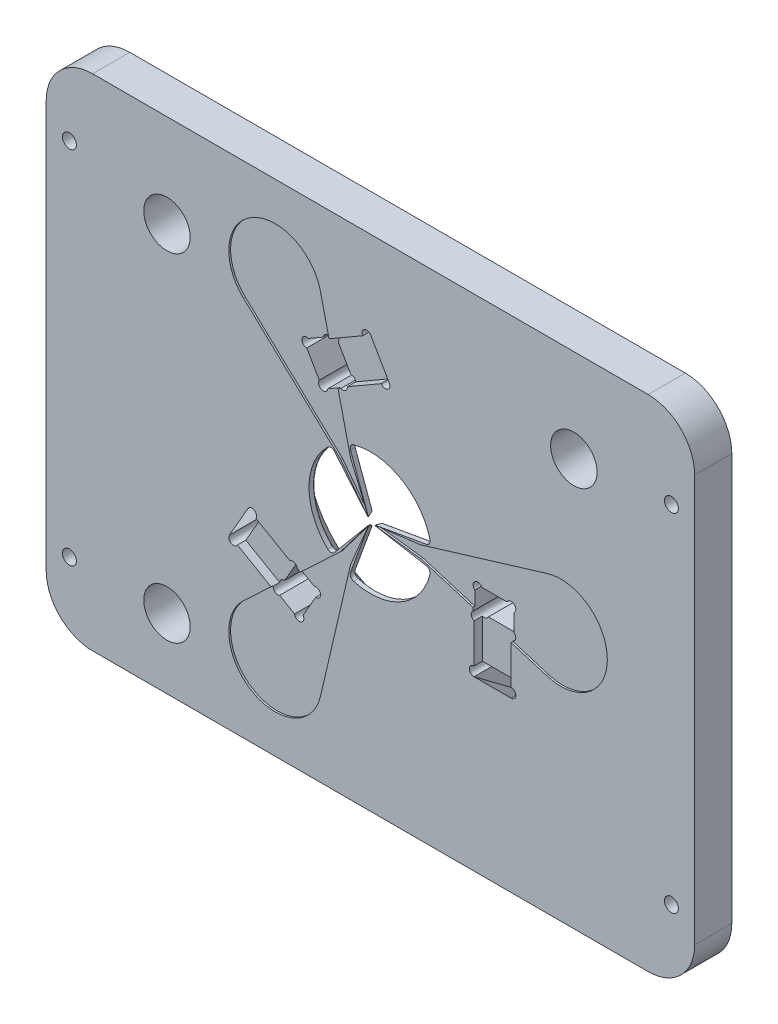
SolidWorks part; units mm, degrees
ref_plane "前基準面" through (0, 0, 0) normal (0, 0, 1) x (1, 0, 0)
ref_plane "上基準面" through (0, 0, 0) normal (0, 1, 0) x (1, 0, 0)
ref_plane "右基準面" through (0, 0, 0) normal (1, 0, 0) x (0, 0, -1)
sketch "草圖1" plane through (0, 0, 0) normal (0, 0, 1) x (1, 0, 0)
  line L1 (-38, 30) -> (38, 30)
  line L2 (-38, 30) -> (-38, -30)
  line L3 (-38, -30) -> (38, -30)
  line L4 (38, 30) -> (38, -30)
  line L5 (-38, 30) -> (38, -30) construction
  line L6 (-38, -30) -> (38, 30) construction
  point P0 (0, 0)
  point P28 (0, 0)
  dimension "D1" = 76
  dimension "D2" = 60
extrude "填料-伸長1" add sketch "草圖1" along normal blind 4
sketch "草圖2" plane through (0, 0, 4) normal (0, 0, 1) x (1, 0, 0)
  line L6 (0.3574, 0.005) -> (20.1903, 2.4807) construction
  line L7 (0.3574, -0.005) -> (20.1903, -2.4807) construction
  line L8 (0.3574, 0.005) -> (4.5094, 0.5233)
  line L9 (0.3574, -0.005) -> (4.5094, -0.5233)
  line L10 (6.1751, 0.8773) -> (19.0478, 4.7845)
  line L11 (6.1751, -0.8773) -> (19.0478, -4.7845)
  line L12 (-2.3278, -5.7864) -> (-5.3804, -18.8881)
  line L13 (-0.1744, -0.312) -> (-1.8015, -4.1669)
  line L14 (-0.183, -0.307) -> (-2.7079, -3.6436)
  line L15 (-3.8473, -4.9091) -> (-13.6674, -14.1037)
  line L16 (-3.8473, 4.9091) -> (-13.6674, 14.1037)
  line L17 (-0.183, 0.307) -> (-2.7079, 3.6436)
  line L18 (-0.1744, 0.312) -> (-1.8015, 4.1669)
  line L19 (-2.3278, 5.7864) -> (-5.3804, 18.8881)
  circle A7 centre (0, 0) radius 0.353 construction
  arc A8 (0.3574, 0.005) -> (0.3574, -0.005) centre (0.358, 0) ccw
  arc A9 (19.0478, -4.7845) -> (19.0478, 4.7845) centre (20.5, 0) ccw
  circle A10 centre (20.5, 0) radius 2.5 construction
  arc A11 (4.5094, -0.5233) -> (6.1751, -0.8773) centre (3.2707, -10.4463) cw
  arc A12 (4.5094, 0.5233) -> (6.1751, 0.8773) centre (3.2707, 10.4463) ccw
  arc A13 (-13.6674, -14.1037) -> (-5.3804, -18.8881) centre (-10.25, -17.7535) ccw
  arc A14 (-1.8015, -4.1669) -> (-2.3278, -5.7864) centre (7.4114, -8.0556) ccw
  arc A15 (-0.1744, -0.312) -> (-0.183, -0.307) centre (-0.179, -0.31) ccw
  arc A16 (-2.7079, -3.6436) -> (-3.8473, -4.9091) centre (-10.6821, 2.3906) cw
  arc A17 (-5.3804, 18.8881) -> (-13.6674, 14.1037) centre (-10.25, 17.7535) ccw
  arc A18 (-2.7079, 3.6436) -> (-3.8473, 4.9091) centre (-10.6821, -2.3906) ccw
  arc A19 (-0.183, 0.307) -> (-0.1744, 0.312) centre (-0.179, 0.31) ccw
  arc A20 (-1.8015, 4.1669) -> (-2.3278, 5.7864) centre (7.4114, 8.0556) cw
  point P17 (5.3574, -0.6291)
  point P20 (5.3574, 0.6291)
  point P46 (0, 0)
  dimension "D1" = 0.706
  dimension "D2" = 0.01
  dimension "D3" = 10
  dimension "D6" = 5
  dimension "D4" = 5
  dimension "D7" = 10
  dimension "D9" = 0.6201
  dimension "D5" = 20.5
  dimension "D8" = 3
extrude "除料-伸長1" cut sketch "草圖2" against normal blind 0.5
sketch "草圖5" plane through (0, 0, 4) normal (0, 0, 1) x (1, 0, 0)
  line L0 (-29.9, 26.9) -> (29.9, 26.9)
  line L1 (-38, 30) -> (-38, -30) construction
  line L2 (38, -30) -> (38, 30) construction
  line L3 (34.9, 21.9) -> (34.9, -21.9)
  line L4 (38, 30) -> (-38, 30) construction
  line L5 (-38, -30) -> (38, -30) construction
  line L6 (-29.9, -26.9) -> (29.9, -26.9)
  line L7 (-34.9, 21.9) -> (-34.9, -21.9)
  arc A0 (-29.9, -26.9) -> (-34.9, -21.9) centre (-29.9, -21.9) cw
  arc A1 (34.9, -21.9) -> (29.9, -26.9) centre (29.9, -21.9) cw
  arc A2 (29.9, 26.9) -> (34.9, 21.9) centre (29.9, 21.9) cw
  arc A3 (-34.9, 21.9) -> (-29.9, 26.9) centre (-29.9, 21.9) cw
  line M29 (38, -30) -> (38, 30)
  line M30 (38, 30) -> (-38, 30)
  line M31 (-38, 30) -> (-38, -30)
  line M32 (-38, -30) -> (38, -30)
  dimension "D5" = 5
  dimension "D1" = 3.1
  dimension "D2" = 3.1
  dimension "D3" = 3.1
  dimension "D4" = 3.1
extrude "除料-伸長4" cut sketch "草圖5" against normal blind 10 contours L7 A3 L0 A2 L3 A1 L6 A0 M32 M29 M30 M31 region at (0, -29.0317, 4)
ref_plane "平面1" through (0, 0, 4) normal (0, 0, 1) x (1, 0, 0)
sketch "草圖7" plane through (0, 0, 4) normal (0, 0, 1) x (1, 0, 0)
  line L0 (0, 0) -> (34.9, 0) construction
  line L1 (34.9, 21.9) -> (34.9, -21.9) construction
  line L2 (11.05, -0.2286) -> (15.25, -0.2286)
  line L3 (15.25, -0.2286) -> (15.25, -3.3286)
  line L4 (15.25, -3.3286) -> (11.05, -3.3286)
  line L5 (11.05, -3.3286) -> (11.05, -0.2286)
  line L6 (11.05, -1.7786) -> (15.25, -1.7786) construction
  line L7 (13.15, -0.2286) -> (13.15, -3.3286) construction
  line L8 (13.15, -1.7786) -> (11.05, -0.2286) construction
  line L9 (0, 0) -> (-12.75, -22.0836) construction
  line L10 (-6.575, -11.3882) -> (-6.9709, -11.1597) construction
  line L11 (-5.7229, -9.4553) -> (-7.8229, -13.0926)
  line L16 (-7.4271, 13.3212) -> (-5.3271, 9.6839)
  line L17 (-7.4271, 13.3212) -> (-4.7424, 14.8712)
  line L18 (-4.7424, 14.8712) -> (-2.6424, 11.2339)
  line L23 (13.15, -1.7786) -> (13.15, -13.7786) construction
  line L24 (11.15, -7.7786) -> (15.15, -7.7786)
  line L25 (11.15, -7.7786) -> (11.15, -8.7786)
  line L26 (11.15, -8.7786) -> (15.15, -8.7786)
  line L27 (15.15, -8.7786) -> (15.15, -7.7786)
  line L28 (-2.6424, 11.2339) -> (-5.3271, 9.6839)
  line L33 (-6.0847, 14.0962) -> (-3.9847, 10.4589) construction
  line L34 (11.15, -8.2786) -> (15.15, -8.2786) construction
  line L35 (-5.7229, -9.4553) -> (-8.4076, -7.9053)
  line L40 (-8.4076, -7.9053) -> (-10.5076, -11.5426)
  line L41 (0, 0) -> (-12.75, 22.0836) construction
  line L42 (-6.575, 11.3882) -> (-6.1791, 11.6168) construction
  line L43 (-6.3771, 11.5025) -> (-3.6924, 13.0525) construction
  line L44 (-10.5076, -11.5426) -> (-7.8229, -13.0926)
  line L45 (-7.0653, -8.6803) -> (-9.1653, -12.3176) construction
  line L46 (-9.4576, -9.7239) -> (-6.7729, -11.2739) construction
  line L47 (-8.4076, -7.9053) -> (-7.8229, -13.0926) construction
  line L48 (-10.5076, -11.5426) -> (-5.7229, -9.4553) construction
  line L49 (-9.4576, -9.7239) -> (-17.1653, -5.2739) construction
  line L50 (-12.3114, -5.7669) -> (-14.3114, -9.231)
  line L51 (-4.7424, 14.8712) -> (-5.3271, 9.6839) construction
  line L52 (-7.4271, 13.3212) -> (-2.6424, 11.2339) construction
  line L53 (-3.6924, 13.0525) -> (4.0153, 17.5025) construction
  line L54 (-0.8386, 17.0096) -> (1.1614, 13.5455)
  line L55 (-0.8386, 17.0096) -> (0.0275, 17.5096)
  line L56 (0.0275, 17.5096) -> (2.0275, 14.0455)
  line L57 (2.0275, 14.0455) -> (1.1614, 13.5455)
  line L58 (-0.4055, 17.2596) -> (1.5945, 13.7955) construction
  line L59 (-4.3091, 13.6779) -> (-3.8841, 12.9418) construction
  line L60 (-4.7841, 14.5007) -> (-4.3091, 13.6779) construction
  line L61 (-12.3114, -5.7669) -> (-13.1775, -5.2669)
  line L62 (-13.1775, -5.2669) -> (-15.1775, -8.731)
  line L63 (-15.1775, -8.731) -> (-14.3114, -9.231)
  line L64 (-12.7445, -5.5169) -> (-14.7445, -8.981) construction
  line L65 (-10.1659, -11.3935) -> (-9.6909, -10.5708) construction
  line L66 (-9.6909, -10.5708) -> (-9.2659, -9.8347) construction
  circle A0 centre (11.35, -0.45) radius 0.5
  circle A1 centre (14.95, -0.45) radius 0.5
  circle A2 centre (14.95, -3.1071) radius 0.5
  circle A3 centre (11.35, -3.1071) radius 0.5
  circle A4 centre (13.15, -0.9886) radius 0.15 construction
  arc A11 (-13.6674, -14.1037) -> (-5.3804, -18.8881) centre (-10.25, -17.7535) ccw construction
  circle A17 centre (-7.0853, 13.1721) radius 0.5
  circle A20 centre (15.15, -8.2786) radius 0.5
  circle A21 centre (11.15, -8.2786) radius 0.5
  arc A24 (-5.3804, 18.8881) -> (-13.6674, 14.1037) centre (-10.25, 17.7535) ccw construction
  circle A25 centre (-7.8647, -12.7221) radius 0.5
  circle A26 centre (-10.1659, -11.3935) radius 0.5
  circle A27 centre (-6.0647, -9.6044) radius 0.5
  circle A28 centre (-8.3659, -8.2758) radius 0.5
  circle A29 centre (-14.7445, -8.981) radius 0.5
  circle A30 centre (-12.7445, -5.5169) radius 0.5
  circle A31 centre (-4.7841, 14.5007) radius 0.5
  circle A32 centre (-2.9841, 11.383) radius 0.5
  circle A33 centre (-5.2853, 10.0544) radius 0.5
  circle A34 centre (-0.4055, 17.2596) radius 0.5
  circle A35 centre (1.5945, 13.7955) radius 0.5
  point P24 (13.15, -7.7786)
  point P37 (-6.7729, -11.2739)
  point P52 (-6.3771, 11.5025)
  point P70 (0.1614, 15.2775)
  point P89 (-13.3114, -7.4989)
  dimension "D3" = 1
  dimension "D4" = 0.3
  dimension "D10" = 13.15
  dimension "D23" = 0.3
  dimension "D17" = 1
  dimension "D24" = 0.45
  dimension "D25" = 4
  dimension "D30" = 0.45
  dimension "D20" = 1
  dimension "D1" = 4.2
  dimension "D2" = 3.1
  dimension "D5" = 0.79
  dimension "D6" = 0.45
  dimension "D7" = 13.15
  dimension "D11" = 13.15
  dimension "D12" = 4.2
  dimension "D13" = 4
  dimension "D14" = 1
  dimension "D15" = 4.2
  dimension "D16" = 3.1
  dimension "D18" = 4.95
  dimension "D19" = 3.1
  dimension "D21" = 0.3
  dimension "D22" = 0.3
  dimension "D26" = 1
  dimension "D27" = 4.95
  dimension "D29" = 1.25
  dimension "D31" = 4
  dimension "D32" = 1
  dimension "D33" = 4.95
  dimension "D35" = 1.25
extrude "除料-伸長5" cut sketch "草圖7" against normal through all contours A2 L3 A1 L2 A0 L5 A3 L4 | A25 A27 | A17 L17 | A35 L56 A34 L54 | A28 L40 A26 L44 A25 L11 A27 L35 | A30 L62 A29 L50 | A2 | A1 | A0 | A3 | A27 | A25 | A17 | L24 L27 L26 L25 | A20 | A21 | A33 | A32 | A31 | A34 | A35 | A26 | A28 | A29 | A30 region at (13.15, -1.7786, 4) region at (-6.1957, -9.613, 4) region at (-8.1153, -10.4989, 4) region at (-5.0347, 12.2775, 4) region at (-13.7445, -7.2489, 4) region at (0.5945, 15.5275, 4)
sketch "草圖9" plane through (0, 0, 4) normal (0, 0, 1) x (1, 0, 0)
  line L0 (34.9, 21.9) -> (24.9, 21.9) construction
  line L1 (24.9, 21.9) -> (24.9, -21.9) construction
  line L2 (24.9, -21.9) -> (34.9, -21.9) construction
  line L3 (34.9, 21.9) -> (34.9, -21.9) construction
  line L4 (0, 26.9) -> (0, -26.9) construction
  line L5 (-29.9, 26.9) -> (29.9, 26.9) construction
  line L6 (-29.9, -26.9) -> (29.9, -26.9) construction
  line L7 (34.9, 0) -> (-34.9, 0) construction
  line L8 (-34.9, 21.9) -> (-34.9, -21.9) construction
  circle A0 centre (32.4, 17.9) radius 0.75
  circle A3 centre (-32.4, 19.4) radius 0.75
  circle A4 centre (-32.4, -19.4) radius 0.75
  circle A5 centre (32.4, -19.4) radius 0.75
  dimension "D2" = 1.5
  dimension "D5" = 2.5
  dimension "D3" = 1.5
  dimension "D7" = 2.5
  dimension "D1" = 10
  dimension "D4" = 4
  dimension "D6" = 2.5
extrude "除料-伸長6" cut sketch "草圖9" against normal through all
sketch "草圖13" plane through (0, 0, 4) normal (0, 0, 1) x (1, 0, 0)
  line L0 (5.358, 0.6292) -> (19.0478, 4.7845) construction
  line L1 (0.3574, 0.005) -> (20.1903, 2.4807) construction
  line L2 (20.1903, -2.4807) -> (0.3574, -0.005) construction
  line L15 (0.3574, 0.005) -> (5.358, 0.6292) construction
  line L16 (0.3574, -0.005) -> (5.358, -0.6292) construction
  line L17 (5.358, -0.6292) -> (19.0478, -4.7845) construction
  line L18 (-2.1341, -4.9548) -> (-5.3804, -18.8881) construction
  line L19 (-0.1744, -0.312) -> (-2.1341, -4.9548) construction
  line L20 (-0.183, -0.307) -> (-3.2239, -4.3256) construction
  line L21 (-3.2239, -4.3256) -> (-13.6673, -14.1036) construction
  line L22 (-3.2239, 4.3256) -> (-13.6673, 14.1036) construction
  line L23 (-0.183, 0.307) -> (-3.2239, 4.3256) construction
  line L24 (-0.1744, 0.312) -> (-2.1341, 4.9548) construction
  line L25 (-2.1341, 4.9548) -> (-5.3804, 18.8881) construction
  line L41 (0.3574, 0.005) -> (6.0148, 0.9981)
  line L42 (0.3574, -0.005) -> (6.0148, -0.9981)
  line L43 (-0.183, -0.307) -> (-3.8718, -4.71)
  line L44 (-0.1744, -0.312) -> (-2.143, -5.708)
  line L45 (-0.1744, 0.312) -> (-2.143, 5.708)
  line L46 (-0.183, 0.307) -> (-3.8718, 4.71)
  circle A8 centre (0, 0) radius 0.353 construction
  arc A9 (0.3574, 0.005) -> (0.3574, -0.005) centre (0.358, 0) ccw construction
  circle A10 centre (20.5, 0) radius 2.5 construction
  arc A11 (19.0478, -4.7845) -> (19.0478, 4.7845) centre (20.5, 0) ccw construction
  arc A12 (-13.6673, -14.1036) -> (-5.3804, -18.8881) centre (-10.25, -17.7535) ccw construction
  arc A13 (-0.1744, -0.312) -> (-0.183, -0.307) centre (-0.179, -0.31) ccw construction
  arc A14 (-5.3804, 18.8881) -> (-13.6673, 14.1036) centre (-10.25, 17.7535) ccw construction
  arc A15 (-0.183, 0.307) -> (-0.1744, 0.312) centre (-0.179, 0.31) ccw construction
  arc A16 (-4.6031, 4.7478) -> (-4.6031, -4.7478) centre (0, 0) ccw
  arc A17 (-0.183, 0.307) -> (-0.1744, 0.312) centre (-0.179, 0.31) ccw
  arc A18 (-0.1744, -0.312) -> (-0.183, -0.307) centre (-0.179, -0.31) ccw
  arc A19 (-1.8102, -6.3603) -> (6.4133, -1.6125) centre (0, 0) ccw
  arc A20 (0.3574, 0.005) -> (0.3574, -0.005) centre (0.358, 0) ccw
  arc A21 (6.4133, 1.6125) -> (-1.8102, 6.3603) centre (0, 0) ccw
  arc A22 (6.0148, -0.9981) -> (6.4133, -1.6125) centre (5.9284, -1.4906) cw
  arc A23 (6.0148, 0.9981) -> (6.4133, 1.6125) centre (5.9284, 1.4906) ccw
  arc A24 (-2.143, 5.708) -> (-1.8102, 6.3603) centre (-1.6733, 5.8794) cw
  arc A25 (-3.8718, 4.71) -> (-4.6031, 4.7478) centre (-4.2551, 4.3888) ccw
  arc A26 (-3.8718, -4.71) -> (-4.6031, -4.7478) centre (-4.2551, -4.3888) cw
  arc A27 (-2.143, -5.708) -> (-1.8102, -6.3603) centre (-1.6733, -5.8794) ccw
  point P31 (0, 0)
  point P38 (6.5229, -1.0873)
  point P41 (6.5229, 1.0873)
  point P49 (0, 0)
  dimension "D1" = 0.706
  dimension "D2" = 0.01
  dimension "D3" = 5
  dimension "D6" = 5
  dimension "D5" = 10
  dimension "D8" = 13.2258
  dimension "D12" = 0.5
  dimension "D13" = 0.5
  dimension "D4" = 20.5
  dimension "D9" = 0.1
  dimension "D10" = 0.1
  dimension "D11" = 3
  dimension "D7" = 3
extrude "除料-伸長8" cut sketch "草圖13" against normal blind 0.5
sketch "草圖12" plane through (0, 0, 3.5) normal (0, 0, 1) x (1, 0, 0)
  line L0 (11.05, -2.357) -> (11.05, -0.85) construction
  line L1 (11.7983, -0.2286) -> (14.5017, -0.2286) construction
  line L2 (15.25, -0.85) -> (15.25, -2.7071) construction
  line L3 (15.0966, -3.5852) -> (19.0478, -4.7845) construction
  line L4 (19.0478, 4.7845) -> (6.1751, 0.8773) construction
  line L5 (4.5094, 0.5233) -> (0.3574, 0.005) construction
  line L6 (0.3574, -0.005) -> (4.5094, -0.5233) construction
  line L7 (6.1751, -0.8773) -> (11.05, -2.357) construction
  line L8 (-10.6531, -11.2814) -> (-13.6674, -14.1037) construction
  line L9 (-5.3804, -18.8881) -> (-2.3278, -5.7864) construction
  line L10 (-1.8015, -4.1669) -> (-0.1744, -0.312) construction
  line L11 (-0.183, -0.307) -> (-2.7079, -3.6436) construction
  line L12 (-3.8473, -4.9091) -> (-7.5662, -8.3911) construction
  line L13 (-7.5662, -8.3911) -> (-6.2611, -9.1446) construction
  line L14 (-6.0971, -10.1033) -> (-7.4488, -12.4446) construction
  line L15 (-8.3611, -12.7819) -> (-9.9695, -11.8533) construction
  line L16 (-3.4838, 10.7481) -> (-4.7889, 9.9946) construction
  line L17 (-5.7012, 10.3319) -> (-7.0529, 12.6731) construction
  line L18 (-6.8889, 13.6319) -> (-5.2805, 14.5605) construction
  line L19 (-4.4434, 14.8666) -> (-5.3804, 18.8881) construction
  line L20 (-13.6674, 14.1037) -> (-3.8473, 4.9091) construction
  line L21 (-2.7079, 3.6436) -> (-0.183, 0.307) construction
  line L22 (-0.1744, 0.312) -> (-1.8015, 4.1669) construction
  line L23 (-2.3278, 5.7864) -> (-3.4838, 10.7481) construction
  line L24 (11.05, -2.357) -> (11.05, -0.85)
  line L25 (11.7983, -0.2286) -> (14.5017, -0.2286)
  line L26 (15.25, -0.85) -> (15.25, -2.7071)
  line L27 (15.0966, -3.5852) -> (19.0478, -4.7845)
  line L28 (19.0478, 4.7845) -> (6.1751, 0.8773)
  line L29 (4.5094, 0.5233) -> (0.3574, 0.005)
  line L30 (0.3574, -0.005) -> (4.5094, -0.5233)
  line L31 (6.1751, -0.8773) -> (11.05, -2.357)
  line L32 (-10.6531, -11.2814) -> (-13.6674, -14.1037)
  line L33 (-5.3804, -18.8881) -> (-2.3278, -5.7864)
  line L34 (-1.8015, -4.1669) -> (-0.1744, -0.312)
  line L35 (-0.183, -0.307) -> (-2.7079, -3.6436)
  line L36 (-3.8473, -4.9091) -> (-7.5662, -8.3911)
  line L37 (-7.5662, -8.3911) -> (-6.2611, -9.1446)
  line L38 (-6.0971, -10.1033) -> (-7.4488, -12.4446)
  line L39 (-8.3611, -12.7819) -> (-9.9695, -11.8533)
  line L40 (-3.4838, 10.7481) -> (-4.7889, 9.9946)
  line L41 (-5.7012, 10.3319) -> (-7.0529, 12.6731)
  line L42 (-6.8889, 13.6319) -> (-5.2805, 14.5605)
  line L43 (-4.4434, 14.8666) -> (-5.3804, 18.8881)
  line L44 (-13.6674, 14.1037) -> (-3.8473, 4.9091)
  line L45 (-2.7079, 3.6436) -> (-0.183, 0.307)
  line L46 (-0.1744, 0.312) -> (-1.8015, 4.1669)
  line L47 (-2.3278, 5.7864) -> (-3.4838, 10.7481)
  arc A0 (11.7983, -0.2286) -> (11.05, -0.85) centre (11.35, -0.45) ccw construction
  arc A1 (15.25, -0.85) -> (14.5017, -0.2286) centre (14.95, -0.45) ccw construction
  arc A2 (15.0966, -3.5852) -> (15.25, -2.7071) centre (14.95, -3.1071) ccw construction
  arc A3 (19.0478, -4.7845) -> (19.0478, 4.7845) centre (20.5, 0) ccw construction
  arc A4 (4.5094, 0.5233) -> (6.1751, 0.8773) centre (3.2707, 10.4463) ccw construction
  arc A6 (6.1751, -0.8773) -> (4.5094, -0.5233) centre (3.2707, -10.4463) ccw construction
  arc A7 (-10.6531, -11.2814) -> (-9.9695, -11.8533) centre (-10.1659, -11.3935) ccw construction
  arc A8 (-13.6674, -14.1037) -> (-5.3804, -18.8881) centre (-10.25, -17.7535) ccw construction
  arc A9 (-1.8015, -4.1669) -> (-2.3278, -5.7864) centre (7.4114, -8.0556) ccw construction
  arc A11 (-3.8473, -4.9091) -> (-2.7079, -3.6436) centre (-10.6821, 2.3906) ccw construction
  arc A12 (-6.0971, -10.1033) -> (-6.2611, -9.1446) centre (-6.0647, -9.6044) ccw construction
  arc A13 (-8.3611, -12.7819) -> (-7.4488, -12.4446) centre (-7.8647, -12.7221) ccw construction
  arc A14 (-5.7012, 10.3319) -> (-4.7889, 9.9946) centre (-5.2853, 10.0544) ccw construction
  arc A15 (-6.8889, 13.6319) -> (-7.0529, 12.6731) centre (-7.0853, 13.1721) ccw construction
  arc A16 (-4.4434, 14.8666) -> (-5.2805, 14.5605) centre (-4.7841, 14.5007) ccw construction
  arc A17 (-5.3804, 18.8881) -> (-13.6674, 14.1037) centre (-10.25, 17.7535) ccw construction
  arc A18 (-2.7079, 3.6436) -> (-3.8473, 4.9091) centre (-10.6821, -2.3906) ccw construction
  arc A20 (-2.3278, 5.7864) -> (-1.8015, 4.1669) centre (7.4114, 8.0556) ccw construction
  arc A21 (11.7983, -0.2286) -> (11.05, -0.85) centre (11.35, -0.45) ccw
  arc A22 (15.25, -0.85) -> (14.5017, -0.2286) centre (14.95, -0.45) ccw
  arc A23 (15.0966, -3.5852) -> (15.25, -2.7071) centre (14.95, -3.1071) ccw
  arc A24 (19.0478, -4.7845) -> (19.0478, 4.7845) centre (20.5, 0) ccw
  arc A25 (4.5094, 0.5233) -> (6.1751, 0.8773) centre (3.2707, 10.4463) ccw
  arc A26 (0.3574, 0.005) -> (0.3574, -0.005) centre (0.358, 0) ccw
  arc A27 (6.1751, -0.8773) -> (4.5094, -0.5233) centre (3.2707, -10.4463) ccw
  arc A28 (-10.6531, -11.2814) -> (-9.9695, -11.8533) centre (-10.1659, -11.3935) ccw
  arc A29 (-13.6674, -14.1037) -> (-5.3804, -18.8881) centre (-10.25, -17.7535) ccw
  arc A30 (-1.8015, -4.1669) -> (-2.3278, -5.7864) centre (7.4114, -8.0556) ccw
  arc A31 (-0.1744, -0.312) -> (-0.183, -0.307) centre (-0.179, -0.31) ccw
  arc A32 (-3.8473, -4.9091) -> (-2.7079, -3.6436) centre (-10.6821, 2.3906) ccw
  arc A33 (-6.0971, -10.1033) -> (-6.2611, -9.1446) centre (-6.0647, -9.6044) ccw
  arc A34 (-8.3611, -12.7819) -> (-7.4488, -12.4446) centre (-7.8647, -12.7221) ccw
  arc A35 (-5.7012, 10.3319) -> (-4.7889, 9.9946) centre (-5.2853, 10.0544) ccw
  arc A36 (-6.8889, 13.6319) -> (-7.0529, 12.6731) centre (-7.0853, 13.1721) ccw
  arc A37 (-4.4434, 14.8666) -> (-5.2805, 14.5605) centre (-4.7841, 14.5007) ccw
  arc A38 (-5.3804, 18.8881) -> (-13.6674, 14.1037) centre (-10.25, 17.7535) ccw
  arc A39 (-2.7079, 3.6436) -> (-3.8473, 4.9091) centre (-10.6821, -2.3906) ccw
  arc A40 (-0.183, 0.307) -> (-0.1744, 0.312) centre (-0.179, 0.31) ccw
  arc A41 (-2.3278, 5.7864) -> (-1.8015, 4.1669) centre (7.4114, 8.0556) ccw
  circle A42 centre (0, 0) radius 0.353 construction
  dimension "D1" = 0.005
extrude "填料-伸長2" add sketch "草圖12" along normal blind 0.5
sketch "草圖15" plane through (0, 0, 0) normal (0, 1, 0) x (1, 0, 0)
  line L0 (0.0275, 0) -> (0.0275, -4.5737) construction
  line L7 (-29.9, 0) -> (29.9, 0) construction
  line L8 (11.0275, 0) -> (0.0275, 0)
  line L10 (0.0275, -3.5) -> (6.6404, -3.5)
  line L11 (-1.8102, -3.5) -> (6.4133, -3.5) construction
  line L12 (6.6404, -3.5) -> (11.0275, 0)
  line L13 (0.0275, -3.5) -> (0.0275, 0)
  dimension "D1" = 6.6129
  dimension "D2" = 11
revolve "除料-旋轉2" cut sketch "草圖15" angle 360 about L0
sketch "草圖16" plane through (0, 0, 0) normal (0, 1, 0) x (1, 0, 0)
  line L0 (0, 0) -> (0, -4.8454) construction
  line L1 (0.353, -4.18) -> (0.353, -3.5)
  line L2 (6.6404, -3.5) -> (0.0137, -3.5) construction
  line L3 (0.353, -3.5) -> (0.7456, -3.5)
  line L4 (0.7456, -3.5) -> (0.353, -4.18)
  line L5 (-29.59, -4) -> (29.59, -4) construction
  dimension "D1" = 0.353
  dimension "D2" = 30
  dimension "D3" = 0.18
revolve "除料-旋轉3" cut sketch "草圖16" angle 360 about L0
sketch "草圖17" plane through (0, 0, 4) normal (0, 0, 1) x (1, 0, 0)
  line L0 (-29.9, 26.9) -> (29.9, 26.9) construction
  line L1 (-34.9, 21.9) -> (-34.9, -21.9) construction
  line L2 (0, 26.9) -> (0, -26.9) construction
  line L3 (-29.9, -26.9) -> (29.9, -26.9) construction
  circle A0 centre (-21.9, 16.9) radius 2.5
  circle A1 centre (21.9, 16.9) radius 2.5
  circle A2 centre (-21.9, -19.4) radius 2.5
  dimension "D3" = 5
  dimension "D4" = 5
  dimension "D1" = 10
  dimension "D2" = 13
  dimension "D5" = 7.5
extrude "除料-伸長9" cut sketch "草圖17" against normal through all
sketch "草圖18" plane through (0, 0, 4) normal (0, 0, 1) x (1, 0, 0)
  line L0 (13.15, -0.2286) -> (13.15, -8.7786) construction
  line L1 (11.7983, -0.2286) -> (14.5017, -0.2286) construction
  line L2 (11.15, -8.7786) -> (15.15, -8.7786) construction
  line L3 (14.2511, -3.3286) -> (11.7983, -3.3286) construction
  line L4 (11.15, -3.3286) -> (15.15, -3.3286)
  line L5 (11.15, -3.3286) -> (11.15, -7.7786)
  line L6 (11.15, -7.7786) -> (15.15, -7.7786)
  line L7 (15.15, -3.3286) -> (15.15, -7.7786)
  line L8 (11.15, -3.3286) -> (15.15, -7.7786) construction
  line L9 (11.15, -7.7786) -> (15.15, -3.3286) construction
  line L10 (-6.3771, 11.5025) -> (1.0275, 15.7775) construction
  line L11 (-5.7012, 10.3319) -> (-7.0529, 12.6731) construction
  line L12 (0.0275, 17.5096) -> (2.0275, 14.0455) construction
  line L13 (-0.8386, 17.0096) -> (1.1614, 13.5455) construction
  line L14 (-0.8386, 17.0096) -> (1.1614, 13.5455)
  line L15 (-0.8386, 17.0096) -> (-4.6924, 14.7846)
  line L16 (-4.6924, 14.7846) -> (-2.6924, 11.3205)
  line L17 (1.1614, 13.5455) -> (-2.6924, 11.3205)
  line L18 (-0.8386, 17.0096) -> (-2.6924, 11.3205) construction
  line L19 (-4.6924, 14.7846) -> (1.1614, 13.5455) construction
  line L20 (-4.2429, 14.0061) -> (-3.0165, 11.8819) construction
  line L21 (-6.7729, -11.2739) -> (-14.1775, -6.9989) construction
  line L22 (-6.0971, -10.1033) -> (-7.4488, -12.4446) construction
  line L23 (-13.1775, -5.2669) -> (-15.1775, -8.731) construction
  line L24 (-12.3114, -5.7669) -> (-14.3114, -9.231) construction
  line L25 (-10.4576, -11.456) -> (-8.4576, -7.9919)
  line L26 (-10.4576, -11.456) -> (-14.3114, -9.231)
  line L27 (-14.3114, -9.231) -> (-12.3114, -5.7669)
  line L28 (-8.4576, -7.9919) -> (-12.3114, -5.7669)
  line L29 (-10.4576, -11.456) -> (-12.3114, -5.7669) construction
  line L30 (-14.3114, -9.231) -> (-8.4576, -7.9919) construction
  line L31 (-8.7818, -8.5533) -> (-10.0082, -10.6776) construction
  point P6 (13.15, -5.5536)
  point P20 (-1.7655, 14.165)
  point P29 (-11.3845, -8.6114)
extrude "除料-伸長10" cut sketch "草圖18" against normal blind 0.9
sketch "草圖20" plane through (0, 0, 4) normal (0, 0, 1) x (1, 0, 0)
  line L0 (20.1903, 2.4807) -> (0.3574, 0.005) construction
  line L1 (0.3574, -0.005) -> (20.1903, -2.4807) construction
  line L2 (0.3574, 0.005) -> (5.358, 0.6292)
  line L3 (0.3574, -0.005) -> (5.358, -0.6292)
  line L4 (5.358, 0.6292) -> (19.0478, 4.7845)
  line L5 (5.358, -0.6292) -> (19.0478, -4.7845)
  line L6 (-0.183, -0.307) -> (-3.2239, -4.3256)
  line L7 (-3.2239, -4.3256) -> (-13.6673, -14.1036)
  line L8 (-2.1341, -4.9548) -> (-5.3804, -18.8881)
  line L9 (-0.1744, -0.312) -> (-2.1341, -4.9548)
  line L10 (-7.9468, -18.7257) -> (-0.1744, -0.312) construction
  line L11 (-0.183, -0.307) -> (-12.2436, -16.245) construction
  line L12 (-0.1744, 0.312) -> (-2.1341, 4.9548)
  line L13 (-2.1341, 4.9548) -> (-5.3804, 18.8881)
  line L14 (-3.2239, 4.3256) -> (-13.6673, 14.1036)
  line L15 (-0.183, 0.307) -> (-3.2239, 4.3256)
  line L16 (-12.2436, 16.245) -> (-0.183, 0.307) construction
  line L17 (-0.1744, 0.312) -> (-7.9468, 18.7257) construction
  circle A0 centre (0, 0) radius 0.353 construction
  arc A1 (0.3574, 0.005) -> (0.3574, -0.005) centre (0.358, 0) ccw
  circle A2 centre (20.5, 0) radius 2.5 construction
  arc A3 (19.0478, -4.7845) -> (19.0478, 4.7845) centre (20.5, 0) ccw
  arc A4 (-0.1744, -0.312) -> (-0.183, -0.307) centre (-0.179, -0.31) ccw
  arc A5 (-13.6673, -14.1036) -> (-5.3804, -18.8881) centre (-10.25, -17.7535) ccw
  circle A6 centre (-10.25, -17.7535) radius 2.5 construction
  arc A7 (-0.183, 0.307) -> (-0.1744, 0.312) centre (-0.179, 0.31) ccw
  arc A8 (-5.3804, 18.8881) -> (-13.6673, 14.1036) centre (-10.25, 17.7535) ccw
  circle A9 centre (-10.25, 17.7535) radius 2.5 construction
  point P38 (0, 0)
  dimension "D1" = 0.706
  dimension "D2" = 0.01
  dimension "D3" = 5
  dimension "D5" = 10
  dimension "D4" = 20.5
  dimension "D6" = 5
  dimension "D7" = 3
extrude "除料-伸長11" cut sketch "草圖20" against normal blind 0.2
sketch "草圖21" plane through (0, 0, 0) normal (0, 1, 0) x (1, 0, 0)
  line L0 (0, 0) -> (0, -4.6448) construction
  line L1 (0.1765, 0) -> (0.1765, -4.18)
  line L2 (10.998, 0) -> (-5.5861, 0) construction
  line L3 (0.1765, -4.18) -> (0.3765, -4.18)
  line L4 (0.3765, -4.18) -> (2.7898, 0)
  line L5 (2.7898, 0) -> (0.1765, 0)
  line L6 (0.4566, -4) -> (5.358, -4) construction
  dimension "D1" = 0.353
  dimension "D2" = 0.2
  dimension "D3" = 0.18
  dimension "D4" = 30
revolve "除料-旋轉4" cut sketch "草圖21" angle 360 about L0
ref_plane "平面2" through (11.15, 0, 0) normal (1, 0, 0) x (0, 0, -1)
sketch "草圖22" plane through (11.15, 0, 0) normal (1, 0, 0) x (0, 0, -1)
  line L1 (-4, -8.7786) -> (0, -8.7786)
  line L3 (0, -8.7786) -> (0, -11.7786)
  line L10 (0, -10.1033) -> (0, -12.4446) construction
  line L11 (0, -11.7786) -> (-4, -8.7786)
  line L13 (0, -7.7786) -> (-3.1, -7.7786)
  line L14 (-3.1, -7.7786) -> (-4, -7.7786)
  line L15 (-4, -7.7786) -> (-4, -8.7786)
  line L16 (-4, -8.7786) -> (0, -8.7786)
  line L17 (0, -8.7786) -> (0, -7.7786)
  line L18 (0, -7.7786) -> (-3.1, -7.7786) construction
  line L19 (-3.1, -7.7786) -> (-4, -7.7786) construction
  line L20 (-4, -7.7786) -> (-4, -8.7786) construction
  line L21 (-4, -8.7786) -> (0, -8.7786) construction
  line L22 (0, -8.7786) -> (0, -7.7786) construction
  dimension "D1" = 0
  dimension "D2" = 3
extrude "除料-伸長12" cut sketch "草圖22" along normal blind 4
ref_plane "平面3" through (-5.575, -9.6562, 0) normal (-0.5, -0.866, 0) x (-0.866, 0.5, 0)
sketch "草圖23" plane through (-5.575, -9.6562, 0) normal (-0.5, -0.866, 0) x (-0.866, 0.5, 0)
  line L1 (8.7786, -4) -> (8.7786, 0)
  line L2 (8.7786, 0) -> (11.7786, 0)
  line L11 (39.3442, 0) -> (-12.4442, 0) construction
  line L12 (11.7786, 0) -> (8.7786, -4)
  line L14 (7.7786, 0) -> (7.7786, -3.1)
  line L15 (7.7786, -3.1) -> (7.7786, -4)
  line L16 (7.7786, -4) -> (8.7786, -4)
  line L17 (8.7786, -4) -> (8.7786, 0)
  line L18 (8.7786, 0) -> (7.7786, 0)
  line L19 (7.7786, 0) -> (7.7786, -3.1) construction
  line L20 (7.7786, -3.1) -> (7.7786, -4) construction
  line L21 (7.7786, -4) -> (8.7786, -4) construction
  line L22 (8.7786, -4) -> (8.7786, 0) construction
  line L23 (8.7786, 0) -> (7.7786, 0) construction
  dimension "D1" = 0
  dimension "D2" = 3
extrude "除料-伸長13" cut sketch "草圖23" along normal blind 4
ref_plane "平面4" through (-7.575, 13.1203, 0) normal (0.5, -0.866, 0) x (-0.866, -0.5, 0)
sketch "草圖24" plane through (-7.575, 13.1203, 0) normal (0.5, -0.866, 0) x (-0.866, -0.5, 0)
  line L5 (-8.7786, -4) -> (-8.7786, 0)
  line L6 (-8.7786, 0) -> (-11.7786, 0)
  line L7 (12.4442, 0) -> (-39.3442, 0) construction
  line L8 (-11.7786, 0) -> (-8.7786, -4)
  line L10 (-7.7786, 0) -> (-8.7786, 0)
  line L11 (-8.7786, 0) -> (-8.7786, -4)
  line L12 (-8.7786, -4) -> (-7.7786, -4)
  line L13 (-7.7786, -4) -> (-7.7786, -3.1)
  line L14 (-7.7786, -3.1) -> (-7.7786, 0)
  line L15 (-7.7786, 0) -> (-8.7786, 0) construction
  line L16 (-8.7786, 0) -> (-8.7786, -4) construction
  line L17 (-8.7786, -4) -> (-7.7786, -4) construction
  line L18 (-7.7786, -4) -> (-7.7786, -3.1) construction
  line L19 (-7.7786, -3.1) -> (-7.7786, 0) construction
  dimension "D1" = 0
  dimension "D2" = 3
extrude "除料-伸長14" cut sketch "草圖24" along normal blind 4
